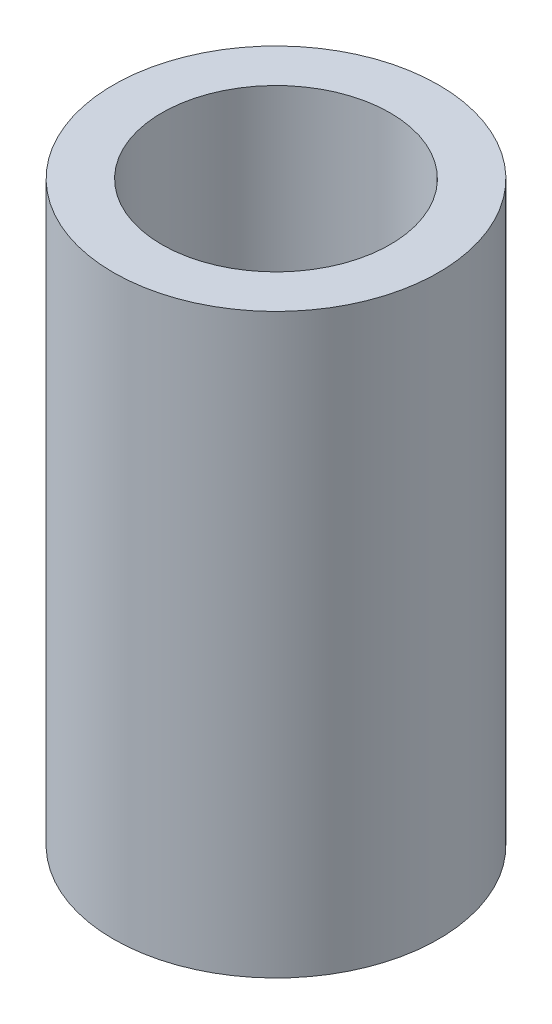
SolidWorks part; units mm, degrees
ref_plane "Front Plane" through (0, 0, 0) normal (0, 0, 1) x (1, 0, 0)
ref_plane "Top Plane" through (0, 0, 0) normal (0, 1, 0) x (1, 0, 0)
ref_plane "Right Plane" through (0, 0, 0) normal (1, 0, 0) x (0, 0, -1)
sketch "Sketch1" plane through (0, 0, 0) normal (0, 1, 0) x (1, 0, 0)
  circle A0 centre (0, 0) radius 25
  dimension "SLEEVE_OD" = 50
extrude "Boss-Extrude1" add sketch "Sketch1" along normal blind 88.7727
sketch "Sketch2" plane through (0, 0, 0) normal (0, 1, 0) x (1, 0, 0)
  circle A0 centre (0, 0) radius 17.556
  dimension "BORE_D" = 35.112
extrude "Cut-Extrude1" cut sketch "Sketch2" along normal through all
chamfer "Chamfer1" distance 2.9727 angle 61.585 rebuild error yes
